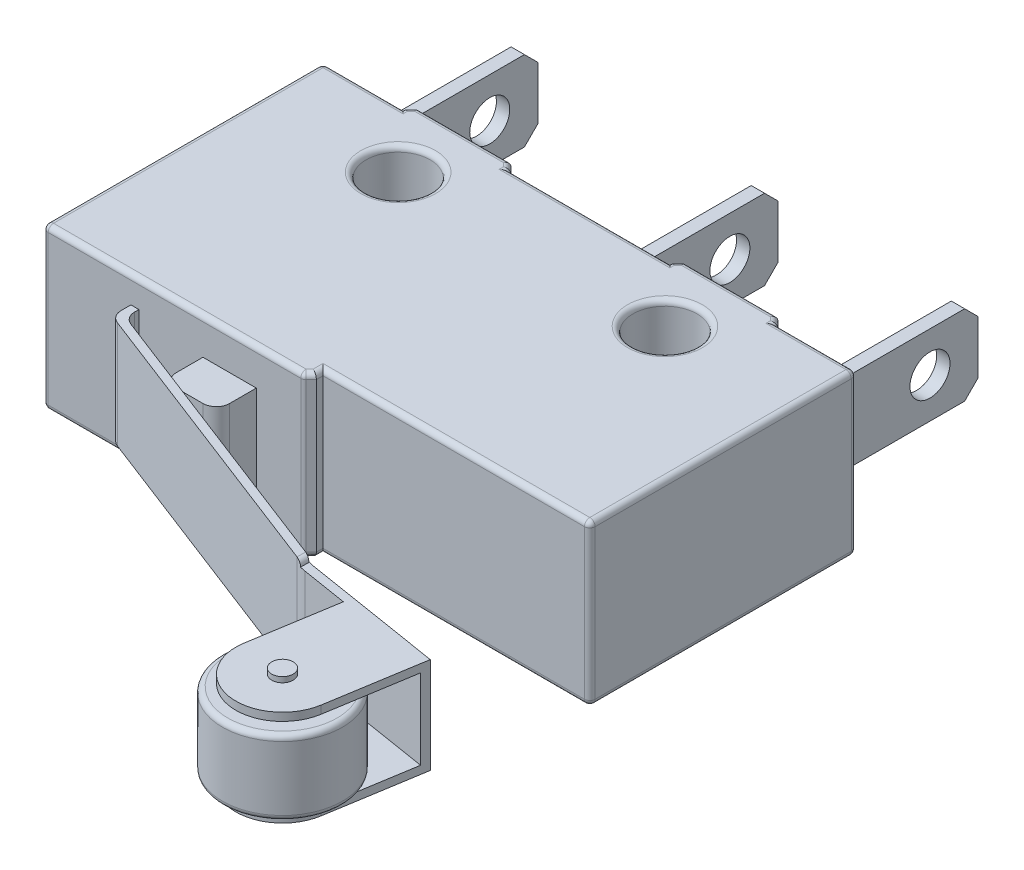
SolidWorks part; units mm, degrees
ref_plane "Front Plane" through (0, 0, 0) normal (0, 0, 1) x (1, 0, 0)
ref_plane "Top Plane" through (0, 0, 0) normal (0, 1, 0) x (1, 0, 0)
ref_plane "Right Plane" through (0, 0, 0) normal (1, 0, 0) x (0, 0, -1)
sketch "Sketch1" plane through (0, 0, 0) normal (0, 1, 0) x (1, 0, 0)
  line L0 (10, 5) -> (-10, -5) construction
  line L1 (-10, 5) -> (10, 5)
  line L2 (-10, 5) -> (-10, -5)
  line L3 (0, -5) -> (10, -5)
  line L4 (10, 5) -> (10, -5)
  line L5 (-10, -5) -> (-10, -5.5)
  line L6 (0, -5.25) -> (-0.25, -5.5)
  line L7 (0, -5.25) -> (0, -5)
  line L8 (-0.25, -5.5) -> (-10, -5.5)
  point P8 (0, -5.5)
  dimension "D1" = 20
  dimension "D2" = 10
extrude "Boss-Extrude1" add sketch "Sketch1" along normal blind 6
sketch "Sketch2" plane through (0, 0, 0) normal (0, -1, 0) x (1, 0, 0)
  line L0 (10, 5) -> (10, -5) construction
  circle A0 centre (-5, -2.8174) radius 1.2
  circle A1 centre (5, -2.8174) radius 1.2
  dimension "D1" = 10
  dimension "D2" = 5
extrude "Cut-Extrude1" cut sketch "Sketch2" against normal up to next
sketch "Sketch3" plane through (0, 0, 0) normal (0, -1, 0) x (1, 0, 0)
  line L0 (-5, -2.8174) -> (-5, -5) construction
  line L1 (10, -5) -> (-10, -5) construction
  line L2 (5, -2.8174) -> (5, -4.0174) construction
  line L3 (5, -4.0174) -> (5, -5) construction
  line L4 (5, -5) -> (5, -5.3) construction
  line L5 (5, -5.3) -> (6.75, -5.3)
  line L6 (7, -5.05) -> (7, -5)
  line L7 (5, -5.3) -> (3.25, -5.3)
  line L8 (3, -5.05) -> (3, -5)
  line L9 (3, -5) -> (7, -5)
  line L10 (3.25, -5.3) -> (3, -5.05)
  line L11 (6.75, -5.3) -> (7, -5.05)
  line L12 (0, 0) -> (0, -5) construction
  line L13 (-5, -5) -> (-5, -5.3) construction
  line L14 (-5, -4.0174) -> (-5, -5) construction
  line L15 (-6.75, -5.3) -> (-7, -5.05)
  line L16 (-3.25, -5.3) -> (-3, -5.05)
  line L17 (-3, -5) -> (-7, -5)
  line L18 (-3, -5.05) -> (-3, -5)
  line L19 (-5, -5.3) -> (-3.25, -5.3)
  line L20 (-7, -5.05) -> (-7, -5)
  line L21 (-5, -5.3) -> (-6.75, -5.3)
  circle A0 centre (5, -2.8174) radius 1.2 construction
  point P13 (7, -5.3)
  point P15 (3, -5.3)
  point P31 (-3, -5.3)
  point P32 (-7, -5.3)
  dimension "D1" = 4
  dimension "D2" = 2
  dimension "D5" = 0.3
extrude "Boss-Extrude2" add sketch "Sketch3" against normal up to surface (6 mm away) up to face at (5, 6, -4.0174)
fillet "Fillet1" radius 0.2 47 edges at (10, 3, 5) (10, 3, -5) (-10, 3, 5.5) (-0.25, 3, 5.5) (-5.125, 0, 5.5) (-0.125, 0, 5.375) (0, 0, 5.125) (5, 0, 5) (10, 0, 0) (6.875, 0, -5.175) (5, 0, -5.3) (3.125, 0, -5.175) (-3, 0, -5.025) (-3.125, 0, -5.175) (-5, 0, -5.3) (-6.875, 0, -5.175) (-7, 0, -5.025) (-10, 0, 0.25) (-5, 0, -4.0174) (5, 0, -4.0174) (-7, 6, -5.025) (-6.875, 6, -5.175) (-5, 6, -5.3) (-3.125, 6, -5.175) (-3, 6, -5.025) (3.125, 6, -5.175) (5, 6, -5.3) (6.875, 6, -5.175) (10, 6, 0) (5, 6, 5) (0, 6, 5.125) (-0.125, 6, 5.375) (-5.125, 6, 5.5) (-10, 6, 0.25) (-5, 6, -4.0174) (5, 6, -4.0174) (-10, 3, -5)
sketch "Sketch4" plane through (0, 0, -5) normal (0, 0, -1) x (-1, 0, 0)
  line L0 (8.2, 1.5) -> (8.2, 4.5) construction
  line L1 (8.45, 1.5) -> (7.95, 1.5)
  line L2 (8.45, 1.5) -> (8.45, 4.5)
  line L3 (8.45, 4.5) -> (7.95, 4.5)
  line L4 (7.95, 1.5) -> (7.95, 4.5)
  line L5 (10, 5.8) -> (10, 0.2) construction
  line L6 (9.8, 3) -> (-9.8, 3) construction
  line L7 (9.8, 0.2) -> (9.8, 5.8) construction
  line L8 (-9.8, 5.8) -> (-9.8, 0.2) construction
  line L9 (8.45, 3) -> (7.95, 3) construction
  line L10 (-0.8, 1.5) -> (-0.8, 4.5) construction
  line L11 (-0.55, 1.5) -> (-1.05, 1.5)
  line L12 (-0.55, 1.5) -> (-0.55, 4.5)
  line L13 (-0.55, 4.5) -> (-1.05, 4.5)
  line L14 (-1.05, 1.5) -> (-1.05, 4.5)
  line L15 (-0.55, 3) -> (-1.05, 3) construction
  line L16 (-8.3, 1.5) -> (-8.3, 4.5) construction
  line L17 (-8.05, 1.5) -> (-8.55, 1.5)
  line L18 (-8.05, 1.5) -> (-8.05, 4.5)
  line L19 (-8.05, 4.5) -> (-8.55, 4.5)
  line L20 (-8.55, 1.5) -> (-8.55, 4.5)
  line L21 (-8.05, 3) -> (-8.55, 3) construction
  dimension "D1" = 0.5
  dimension "D2" = 1.8
  dimension "D3" = 3
  dimension "D4" = 0
  dimension "D5" = 0.5
  dimension "D6" = 3
  dimension "D7" = 0.5
  dimension "D8" = 3
  dimension "D9" = 0
  dimension "D10" = 0
  dimension "D11" = 9
  dimension "D12" = 16.5
extrude "Boss-Extrude3" add sketch "Sketch4" along normal blind 6
chamfer "Chamfer1" distance 0.5 angle 45 6 edges at (-8.2, 1.5, -11) (0.8, 1.5, -11) (8.3, 1.5, -11) (8.3, 4.5, -11) (0.8, 4.5, -11) (-8.2, 4.5, -11)
sketch "Sketch5" plane through (-8.45, 0, 0) normal (-1, 0, 0) x (0, 0, 1)
  line L0 (-11, 3) -> (-9.2, 3) construction
  line L1 (-11, 2) -> (-11, 4) construction
  circle A0 centre (-9.2, 3) radius 0.75
extrude "Cut-Extrude2" cut sketch "Sketch5" against normal up to surface (17 mm away) up to face at (8.55, 3, -8.8333)
sketch "Sketch6" plane through (0, 0, 5.5) normal (0, 0, 1) x (1, 0, 0)
  line L0 (-2, 3) -> (-4, 3) construction
  line L1 (-2, 4.65) -> (-4, 4.65)
  line L2 (-2, 4.65) -> (-2, 1.35)
  line L3 (-2, 1.35) -> (-4, 1.35)
  line L4 (-4, 4.65) -> (-4, 1.35)
  line L5 (-9.8, 3) -> (8.9601, 3) construction
  line L6 (-9.8, 5.8) -> (-9.8, 0.2) construction
  line L7 (-10, 0.2) -> (-10, 5.8) construction
  dimension "D1" = 3.3
  dimension "D2" = 2
  dimension "D3" = 6
extrude "Boss-Extrude4" add sketch "Sketch6" along normal blind 1.5
fillet "Fillet2" radius 0.5 2 edges at (-4, 3, 7) (-2, 3, 7)
sketch "Sketch7" plane through (0, 0, 5.5) normal (0, 0, 1) x (1, 0, 0)
  line L0 (-9.8, 3) -> (-0.3328, 3) construction
  line L1 (-9.8, 5.8) -> (-9.8, 0.2) construction
  line L2 (-0.3328, 0.2) -> (-0.3328, 5.8) construction
  line L3 (-6.4, 3) -> (-6.7, 3) construction
  line L4 (-6.7, 5) -> (-6.4, 5)
  line L5 (-6.7, 5) -> (-6.7, 1)
  line L6 (-6.7, 1) -> (-6.4, 1)
  line L7 (-6.4, 5) -> (-6.4, 1)
  line L8 (-10, 0.2) -> (-10, 5.8) construction
  dimension "D1" = 0.3
  dimension "D2" = 4
  dimension "D3" = 3.3
extrude "Boss-Extrude5" add sketch "Sketch7" along normal blind 0.5
sketch "Sketch8" plane through (0, 1, 0) normal (0, -1, 0) x (1, 0, 0)
  line L0 (-6.4, 6) -> (4.7943, 10.3229)
  line L1 (4.7943, 10.3229) -> (4.7943, 10.6445)
  line L2 (4.7943, 10.6445) -> (-6.7, 6.2057)
  line L3 (-6.7, 6.2057) -> (-6.7, 6)
  line L4 (-6.4, 6) -> (-6.7, 6)
  dimension "D1" = 0.3
  dimension "D2" = 12
extrude "Boss-Extrude6" add sketch "Sketch8" against normal up to surface (4 mm away) up to face at (-6.55, 5, 5.75)
fillet "Fillet3" radius 0.5 2 edges at (-6.4, 3, 6) (-6.7, 3, 6.2057)
sketch "Sketch9" plane through (0, 1, 0) normal (0, -1, 0) x (1, 0, 0)
  line L0 (4.7943, 10.3229) -> (10.2234, 11.203)
  line L1 (10.2234, 11.203) -> (10.1726, 11.5163)
  line L2 (4.7943, 10.6445) -> (10.1726, 11.5163)
  line L3 (4.7943, 10.6445) -> (4.7943, 10.3229)
extrude "Boss-Extrude7" add sketch "Sketch9" against normal blind 3.8
sketch "Sketch10" plane through (0, 1, 0) normal (0, -1, 0) x (1, 0, 0)
  line L0 (10.2234, 11.203) -> (10.1726, 11.5163)
  line L1 (10.1726, 11.5163) -> (4.7943, 10.6445)
  line L2 (4.8451, 10.3311) -> (4.7943, 10.3229)
  line L3 (4.7943, 10.3229) -> (10.2234, 11.203) construction
  line L4 (4.8451, 10.3311) -> (10.2234, 11.203)
  line L5 (4.7943, 10.3229) -> (4.7943, 10.6445)
extrude "Cut-Extrude3" cut sketch "Sketch10" against normal blind 0.2
fillet "Fillet4" radius 2 2 edges tangent propagation no
sketch "Sketch11" plane through (-1.5586, 0, 9.6146) normal (-0.16, 0, 0.9871) x (0.9871, 0, 0.16)
  line L0 (11.8844, 3) -> (6.6444, 3) construction
  line L1 (11.8844, 1.2) -> (8.3844, 1.2)
  line L2 (11.8844, 1.2) -> (11.8844, 1.5)
  line L3 (11.8844, 1.5) -> (8.3844, 1.5)
  line L4 (8.3844, 1.2) -> (8.3844, 1.5)
  line L5 (11.8844, 4.8) -> (11.8844, 1.2) construction
  line L6 (6.6444, 4.8) -> (6.6444, 1.2) construction
  line L7 (8.3844, 4.8) -> (8.3844, 4.5)
  line L8 (11.8844, 4.5) -> (8.3844, 4.5)
  line L9 (11.8844, 4.8) -> (11.8844, 4.5)
  line L10 (11.8844, 4.8) -> (8.3844, 4.8)
  dimension "D1" = 3.5
  dimension "D2" = 0.3
extrude "Boss-Extrude8" add sketch "Sketch11" along normal blind 5
sketch "Sketch12" plane through (0, 1.2, 0) normal (0, -1, 0) x (1, 0, 0)
  line L0 (7.6451, 16.1719) -> (8.2052, 12.717) construction
  line L1 (5.9176, 15.8918) -> (9.3725, 16.4519) construction
  line L2 (7.9251, 14.4444) -> (9.6526, 14.7245) construction
  line L3 (10.2234, 11.203) -> (9.3725, 16.4519) construction
  line L4 (7.6451, 16.1719) -> (5.9176, 15.8918)
  line L5 (5.9176, 15.8918) -> (6.1977, 14.1644)
  line L7 (7.6451, 16.1719) -> (9.3725, 16.4519)
  line L8 (9.3725, 16.4519) -> (9.6526, 14.7245)
  arc A0 (9.6526, 14.7245) -> (6.1977, 14.1644) centre (7.9251, 14.4444) ccw
  line M1 (10.2234, 11.203) -> (9.3725, 16.4519)
  line M2 (9.3725, 16.4519) -> (5.9176, 15.8918)
  line M3 (5.9176, 15.8918) -> (6.7178, 10.9563)
extrude "Cut-Extrude4" cut sketch "Sketch12" against normal up to surface (3.6 mm away) contours A0 M2 M3 | A0 M1 M2 region at (6.3661, 1.2, 15.5685) region at (9.0492, 1.2, 16.0035) up to face at (6.0846, 4.8, 11.8514)
sketch "Sketch13" plane through (0, 1.5, 0) normal (0, 1, 0) x (1, 0, 0)
  circle A0 centre (7.9251, -14.4444) radius 2.25
  point P0 (7.9251, -14.4444)
extrude "Boss-Extrude9" add sketch "Sketch13" along normal blind 2.9
ref_plane "Plane1" through (10.1751, 0, 0) normal (1, 0, 0) x (0, 0, -1)
sketch "Sketch14" plane through (10.1751, 0, 0) normal (1, 0, 0) x (0, 0, -1)
  line L0 (-16.6944, 1.5) -> (-12.7684, 1.5) construction
  line L1 (-17.328, 1.6) -> (-11.828, 1.6)
  line L2 (-17.328, 1.6) -> (-17.328, 1.5)
  line L3 (-17.328, 1.5) -> (-11.828, 1.5)
  line L4 (-11.828, 1.6) -> (-11.828, 1.5)
  dimension "D1" = 0.1
  dimension "D2" = 5.5
extrude "Cut-Extrude5" cut sketch "Sketch14" against normal up to next
fillet "Fillet6" radius 0.2 2 edges at (5.6751, 1.6, 14.4444) (5.6751, 4.4, 14.4444)
sketch "Sketch15" plane through (0, 1.2, 0) normal (0, -1, 0) x (1, 0, 0)
  circle A0 centre (7.9251, 14.4444) radius 0.4
  point P0 (7.9251, 14.4444)
extrude "Boss-Extrude10" add sketch "Sketch15" along normal blind 0.2
sketch "Sketch16" plane through (0, 1, 0) normal (0, -1, 0) x (1, 0, 0)
  circle A1 centre (7.9251, 14.4444) radius 0.4
  circle A2 centre (7.9251, 14.4444) radius 0.4
  dimension "D1" = 0
extrude "Boss-Extrude11" add sketch "Sketch16" against normal blind 4
fillet "Fillet7" radius 0.2 2 edges at (4.7943, 5, 10.478) (4.7943, 1, 10.478)
